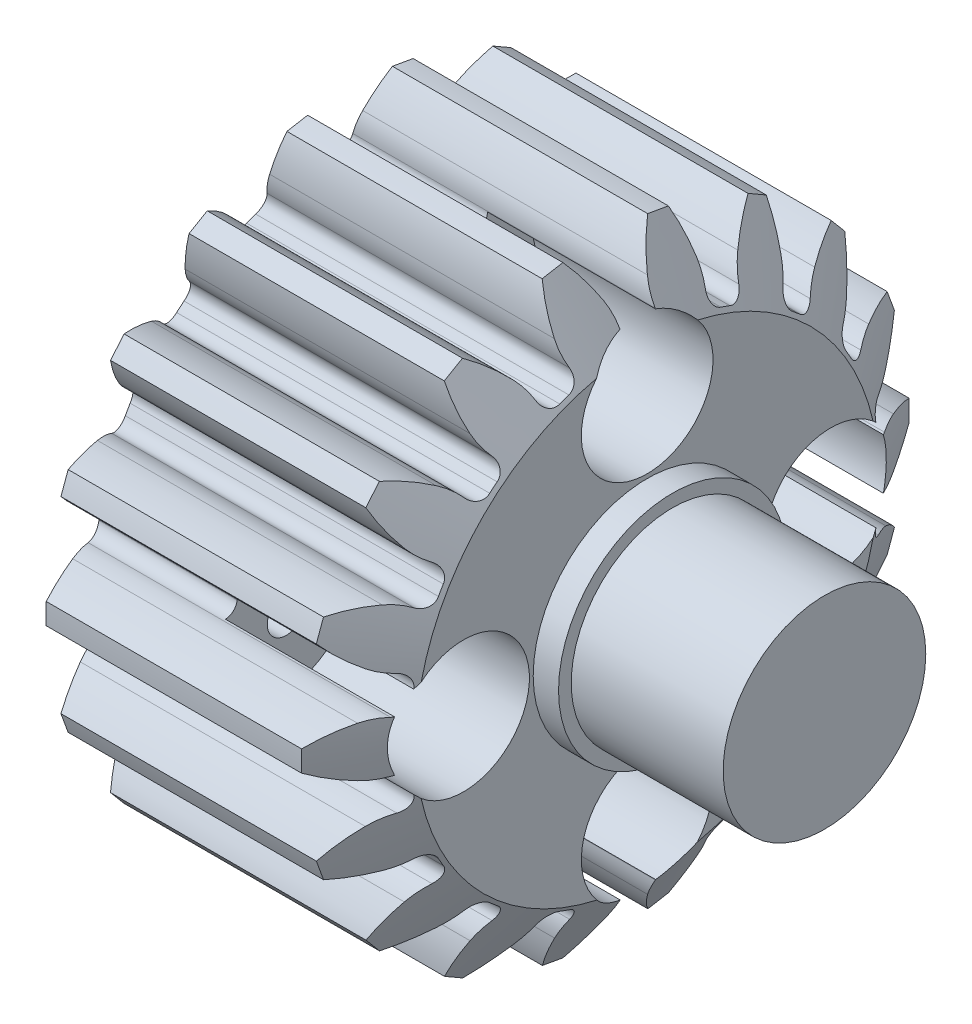
SolidWorks part; units mm, degrees
ref_plane "Front Plane" through (0, 0, 0) normal (0, 0, 1) x (1, 0, 0)
ref_plane "Top Plane" through (0, 0, 0) normal (0, 1, 0) x (1, 0, 0)
ref_plane "Right Plane" through (0, 0, 0) normal (1, 0, 0) x (0, 0, -1)
sketch "Sketch1" plane through (0, 0, 0) normal (1, 0, 0) x (0, 0, -1)
  line L0 (-201.8276, 36.4588) -> (-169.5724, 36.4588) construction
  line L1 (-185.7, 23.0219) -> (-185.7, 49.8958) construction
  line L2 (-185.7, 36.4588) -> (-183.3021, 50.0583) construction
  circle A0 centre (-185.7, 36.4588) radius 9.3 construction
  circle A1 centre (-185.7, 43.7088) radius 0.75
  circle A2 centre (-178.45, 36.4588) radius 0.75
  circle A3 centre (-185.7, 29.2088) radius 0.75
  circle A4 centre (-192.95, 36.4588) radius 0.75
  circle A5 centre (-185.7, 36.4588) radius 12 construction
  arc A7 (-183.2083, 48.1973) -> (-184.0267, 48.3416) centre (-185.7, 36.4588) ccw
  arc A8 (-185.7, 45.7588) -> (-185.5087, 45.7569) centre (-185.7, 36.4588) cw
  arc A9 (-185.5087, 45.7569) -> (-185.0008, 46.2349) centre (-185.4785, 46.2336) ccw
  arc A10 (-185.0008, 46.2349) -> (-184.832, 47.0472) centre (-182.988, 46.2402) cw
  arc A11 (-184.832, 47.0472) -> (-184.0267, 48.3416) centre (-179.9662, 44.9177) cw
  arc A12 (-182.8942, 46.7056) -> (-183.2083, 48.1973) centre (-188.1949, 46.3686) ccw
  arc A13 (-183.0134, 45.8844) -> (-182.8942, 46.7056) centre (-184.9031, 46.5779) ccw
  arc A14 (-182.6997, 45.2616) -> (-183.0134, 45.8844) centre (-182.565, 45.7199) cw
  arc A15 (-182.5192, 45.198) -> (-182.6997, 45.2616) centre (-185.7, 36.4588) ccw
  arc A16 (-182.5192, 45.198) -> (-182.3401, 45.1307) centre (-185.7, 36.4588) cw
  arc A17 (-182.3401, 45.1307) -> (-181.6994, 45.4062) centre (-182.1487, 45.5684) ccw
  arc A18 (-181.6994, 45.4062) -> (-181.2629, 46.1118) centre (-179.8061, 44.7227) cw
  arc A19 (-181.2629, 46.1118) -> (-180.0635, 47.0527) centre (-177.4189, 42.4465) cw
  arc A20 (-179.3437, 46.6371) -> (-180.0635, 47.0527) centre (-185.7, 36.4588) ccw
  arc A21 (-179.5588, 45.128) -> (-179.3437, 46.6371) centre (-184.6551, 46.6243) ccw
  arc A22 (-179.9517, 44.3971) -> (-179.5588, 45.128) centre (-181.4902, 45.6951) ccw
  arc A23 (-179.8699, 43.7045) -> (-179.9517, 44.3971) centre (-179.5866, 44.0891) cw
  arc A24 (-179.7221, 43.5831) -> (-179.8699, 43.7045) centre (-185.7, 36.4588) ccw
  arc A25 (-179.7221, 43.5831) -> (-179.5768, 43.4586) centre (-185.7, 36.4588) cw
  arc A26 (-179.5768, 43.4586) -> (-178.8805, 43.4983) centre (-179.2472, 43.8044) ccw
  arc A27 (-178.8805, 43.4983) -> (-178.229, 44.0121) centre (-177.3351, 42.2085) cw
  arc A28 (-178.229, 44.0121) -> (-176.7801, 44.486) centre (-175.8704, 39.2531) cw
  arc A29 (-176.2459, 43.8493) -> (-176.7801, 44.486) centre (-185.7, 36.4588) ccw
  arc A30 (-176.9642, 42.5048) -> (-176.2459, 43.8493) centre (-181.2413, 45.6539) ccw
  arc A31 (-177.5833, 41.9523) -> (-176.9642, 42.5048) centre (-178.5851, 43.6982) ccw
  arc A32 (-177.7433, 41.2735) -> (-177.5833, 41.9523) centre (-177.3455, 41.538) cw
  arc A33 (-177.646, 41.1088) -> (-177.7433, 41.2735) centre (-185.7, 36.4588) ccw
  arc A34 (-177.646, 41.1088) -> (-177.552, 40.9422) centre (-185.7, 36.4588) cw
  arc A35 (-177.552, 40.9422) -> (-176.8841, 40.7414) centre (-177.1241, 41.1544) ccw
  arc A36 (-176.8841, 40.7414) -> (-176.0962, 41.0013) centre (-175.8731, 39.0008) cw
  arc A37 (-176.0962, 41.0013) -> (-174.5726, 40.9511) centre (-175.5075, 35.7226) cw
  arc A38 (-174.2883, 40.1701) -> (-174.5726, 40.9511) centre (-185.7, 36.4588) ccw
  arc A39 (-175.4232, 39.1523) -> (-174.2883, 40.1701) centre (-178.3653, 43.5744) ccw
  arc A40 (-176.1939, 38.845) -> (-175.4232, 39.1523) centre (-176.5382, 40.8282) ccw
  arc A41 (-176.5764, 38.2618) -> (-176.1939, 38.845) centre (-176.1122, 38.3743) cw
  arc A42 (-176.5413, 38.0738) -> (-176.5764, 38.2618) centre (-185.7, 36.4588) ccw
  arc A43 (-176.5413, 38.0738) -> (-176.51, 37.885) centre (-185.7, 36.4588) cw
  arc A44 (-176.51, 37.885) -> (-175.9511, 37.4679) centre (-176.0353, 37.9381) ccw
  arc A45 (-175.9511, 37.4679) -> (-175.1217, 37.4427) centre (-175.5963, 35.4865) cw
  arc A46 (-175.1217, 37.4427) -> (-173.7072, 36.8744) centre (-176.374, 32.281) cw
  arc A47 (-173.7072, 36.0433) -> (-173.7072, 36.8744) centre (-185.7, 36.4588) ccw
  arc A48 (-175.1217, 35.475) -> (-173.7072, 36.0433) centre (-176.374, 40.6367) ccw
  arc A49 (-175.9511, 35.4498) -> (-175.1217, 35.475) centre (-175.5963, 37.4312) ccw
  arc A50 (-176.51, 35.0327) -> (-175.9511, 35.4498) centre (-176.0353, 34.9796) cw
  arc A51 (-176.5413, 34.8439) -> (-176.51, 35.0327) centre (-185.7, 36.4588) ccw
  arc A52 (-176.5413, 34.8439) -> (-176.5764, 34.6559) centre (-185.7, 36.4588) cw
  arc A53 (-176.5764, 34.6559) -> (-176.1939, 34.0727) centre (-176.1122, 34.5434) ccw
  arc A54 (-176.1939, 34.0727) -> (-175.4232, 33.7653) centre (-176.5382, 32.0895) cw
  arc A55 (-175.4232, 33.7653) -> (-174.2883, 32.7475) centre (-178.3653, 29.3433) cw
  arc A56 (-174.5726, 31.9666) -> (-174.2883, 32.7475) centre (-185.7, 36.4588) ccw
  arc A57 (-176.0962, 31.9164) -> (-174.5726, 31.9666) centre (-175.5075, 37.195) ccw
  arc A58 (-176.8841, 32.1763) -> (-176.0962, 31.9164) centre (-175.8731, 33.9169) ccw
  arc A59 (-177.552, 31.9755) -> (-176.8841, 32.1763) centre (-177.1241, 31.7633) cw
  arc A60 (-177.646, 31.8088) -> (-177.552, 31.9755) centre (-185.7, 36.4588) ccw
  arc A61 (-177.646, 31.8088) -> (-177.7433, 31.6441) centre (-185.7, 36.4588) cw
  arc A62 (-177.7433, 31.6441) -> (-177.5833, 30.9653) centre (-177.3455, 31.3797) ccw
  arc A63 (-177.5833, 30.9653) -> (-176.9642, 30.4129) centre (-178.5851, 29.2195) cw
  arc A64 (-176.9642, 30.4129) -> (-176.2459, 29.0683) centre (-181.2413, 27.2638) cw
  arc A65 (-176.7801, 28.4317) -> (-176.2459, 29.0683) centre (-185.7, 36.4588) ccw
  arc A66 (-178.229, 28.9056) -> (-176.7801, 28.4317) centre (-175.8704, 33.6646) ccw
  arc A67 (-178.8805, 29.4194) -> (-178.229, 28.9056) centre (-177.3351, 30.7092) ccw
  arc A68 (-179.5768, 29.4591) -> (-178.8805, 29.4194) centre (-179.2472, 29.1133) cw
  arc A69 (-179.7221, 29.3346) -> (-179.5768, 29.4591) centre (-185.7, 36.4588) ccw
  arc A70 (-179.7221, 29.3346) -> (-179.8699, 29.2132) centre (-185.7, 36.4588) cw
  arc A71 (-179.8699, 29.2132) -> (-179.9517, 28.5206) centre (-179.5866, 28.8286) ccw
  arc A72 (-179.9517, 28.5206) -> (-179.5588, 27.7897) centre (-181.4902, 27.2226) cw
  arc A73 (-179.5588, 27.7897) -> (-179.3437, 26.2805) centre (-184.6551, 26.2934) cw
  arc A74 (-180.0635, 25.865) -> (-179.3437, 26.2805) centre (-185.7, 36.4588) ccw
  arc A75 (-181.2629, 26.8059) -> (-180.0635, 25.865) centre (-177.4189, 30.4712) ccw
  arc A76 (-181.6994, 27.5115) -> (-181.2629, 26.8059) centre (-179.8061, 28.195) ccw
  arc A77 (-182.3401, 27.787) -> (-181.6994, 27.5115) centre (-182.1487, 27.3493) cw
  arc A78 (-182.5192, 27.7197) -> (-182.3401, 27.787) centre (-185.7, 36.4588) ccw
  arc A79 (-182.5192, 27.7197) -> (-182.6997, 27.6561) centre (-185.7, 36.4588) cw
  arc A80 (-182.6997, 27.6561) -> (-183.0134, 27.0333) centre (-182.565, 27.1978) ccw
  arc A81 (-183.0134, 27.0333) -> (-182.8942, 26.2121) centre (-184.9031, 26.3398) cw
  arc A82 (-182.8942, 26.2121) -> (-183.2083, 24.7204) centre (-188.1949, 26.5491) cw
  arc A83 (-184.0267, 24.5761) -> (-183.2083, 24.7204) centre (-185.7, 36.4588) ccw
  arc A84 (-184.832, 25.8704) -> (-184.0267, 24.5761) centre (-179.9662, 28) ccw
  arc A85 (-185.0008, 26.6828) -> (-184.832, 25.8704) centre (-182.988, 26.6775) ccw
  arc A86 (-185.5087, 27.1608) -> (-185.0008, 26.6828) centre (-185.4785, 26.6841) cw
  arc A87 (-185.7, 27.1588) -> (-185.5087, 27.1608) centre (-185.7, 36.4588) ccw
  arc A88 (-185.7, 27.1588) -> (-185.8913, 27.1608) centre (-185.7, 36.4588) cw
  arc A89 (-185.8913, 27.1608) -> (-186.3992, 26.6828) centre (-185.9215, 26.6841) ccw
  arc A90 (-186.3992, 26.6828) -> (-186.568, 25.8704) centre (-188.412, 26.6775) cw
  arc A91 (-186.568, 25.8704) -> (-187.3733, 24.5761) centre (-191.4338, 28) cw
  arc A92 (-188.1917, 24.7204) -> (-187.3733, 24.5761) centre (-185.7, 36.4588) ccw
  arc A93 (-188.5058, 26.2121) -> (-188.1917, 24.7204) centre (-183.2051, 26.5491) ccw
  arc A94 (-188.3866, 27.0333) -> (-188.5058, 26.2121) centre (-186.4969, 26.3398) ccw
  arc A95 (-188.7003, 27.6561) -> (-188.3866, 27.0333) centre (-188.835, 27.1978) cw
  arc A96 (-188.8808, 27.7197) -> (-188.7003, 27.6561) centre (-185.7, 36.4588) ccw
  arc A97 (-188.8808, 27.7197) -> (-189.0599, 27.787) centre (-185.7, 36.4588) cw
  arc A98 (-189.0599, 27.787) -> (-189.7006, 27.5115) centre (-189.2513, 27.3493) ccw
  arc A99 (-189.7006, 27.5115) -> (-190.1371, 26.8059) centre (-191.5939, 28.195) cw
  arc A100 (-190.1371, 26.8059) -> (-191.3365, 25.865) centre (-193.9811, 30.4712) cw
  arc A101 (-192.0563, 26.2805) -> (-191.3365, 25.865) centre (-185.7, 36.4588) ccw
  arc A102 (-191.8412, 27.7897) -> (-192.0563, 26.2805) centre (-186.7449, 26.2934) ccw
  arc A103 (-191.4483, 28.5206) -> (-191.8412, 27.7897) centre (-189.9098, 27.2226) ccw
  arc A104 (-191.5301, 29.2132) -> (-191.4483, 28.5206) centre (-191.8134, 28.8286) cw
  arc A105 (-191.6779, 29.3346) -> (-191.5301, 29.2132) centre (-185.7, 36.4588) ccw
  arc A106 (-191.6779, 29.3346) -> (-191.8232, 29.4591) centre (-185.7, 36.4588) cw
  arc A107 (-191.8232, 29.4591) -> (-192.5195, 29.4194) centre (-192.1528, 29.1133) ccw
  arc A108 (-192.5195, 29.4194) -> (-193.171, 28.9056) centre (-194.0649, 30.7092) cw
  arc A109 (-193.171, 28.9056) -> (-194.6199, 28.4317) centre (-195.5296, 33.6646) cw
  arc A110 (-195.1541, 29.0683) -> (-194.6199, 28.4317) centre (-185.7, 36.4588) ccw
  arc A111 (-194.4358, 30.4129) -> (-195.1541, 29.0683) centre (-190.1587, 27.2638) ccw
  arc A112 (-193.8167, 30.9653) -> (-194.4358, 30.4129) centre (-192.8149, 29.2195) ccw
  arc A113 (-193.6567, 31.6441) -> (-193.8167, 30.9653) centre (-194.0544, 31.3797) cw
  arc A114 (-193.754, 31.8088) -> (-193.6567, 31.6441) centre (-185.7, 36.4588) ccw
  arc A115 (-193.754, 31.8088) -> (-193.848, 31.9755) centre (-185.7, 36.4588) cw
  arc A116 (-193.848, 31.9755) -> (-194.5159, 32.1763) centre (-194.2759, 31.7633) ccw
  arc A117 (-194.5159, 32.1763) -> (-195.3038, 31.9164) centre (-195.5269, 33.9169) cw
  arc A118 (-195.3038, 31.9164) -> (-196.8274, 31.9666) centre (-195.8925, 37.195) cw
  arc A119 (-197.1117, 32.7475) -> (-196.8274, 31.9666) centre (-185.7, 36.4588) ccw
  arc A120 (-195.9768, 33.7653) -> (-197.1117, 32.7475) centre (-193.0347, 29.3433) ccw
  arc A121 (-195.2061, 34.0727) -> (-195.9768, 33.7653) centre (-194.8618, 32.0895) ccw
  arc A122 (-194.8236, 34.6559) -> (-195.2061, 34.0727) centre (-195.2878, 34.5434) cw
  arc A123 (-194.8587, 34.8439) -> (-194.8236, 34.6559) centre (-185.7, 36.4588) ccw
  arc A124 (-194.8587, 34.8439) -> (-194.89, 35.0327) centre (-185.7, 36.4588) cw
  arc A125 (-194.89, 35.0327) -> (-195.4489, 35.4498) centre (-195.3647, 34.9796) ccw
  arc A126 (-195.4489, 35.4498) -> (-196.2783, 35.475) centre (-195.8037, 37.4312) cw
  arc A127 (-196.2783, 35.475) -> (-197.6928, 36.0433) centre (-195.026, 40.6367) cw
  arc A128 (-197.6928, 36.8744) -> (-197.6928, 36.0433) centre (-185.7, 36.4588) ccw
  arc A129 (-196.2783, 37.4427) -> (-197.6928, 36.8744) centre (-195.026, 32.281) ccw
  arc A130 (-195.4489, 37.4679) -> (-196.2783, 37.4427) centre (-195.8037, 35.4865) ccw
  arc A131 (-194.89, 37.885) -> (-195.4489, 37.4679) centre (-195.3647, 37.9381) cw
  arc A132 (-194.8587, 38.0738) -> (-194.89, 37.885) centre (-185.7, 36.4588) ccw
  arc A133 (-194.8587, 38.0738) -> (-194.8236, 38.2618) centre (-185.7, 36.4588) cw
  arc A134 (-194.8236, 38.2618) -> (-195.2061, 38.845) centre (-195.2878, 38.3743) ccw
  arc A135 (-195.2061, 38.845) -> (-195.9768, 39.1523) centre (-194.8618, 40.8282) cw
  arc A136 (-195.9768, 39.1523) -> (-197.1117, 40.1701) centre (-193.0347, 43.5744) cw
  arc A137 (-196.8274, 40.9511) -> (-197.1117, 40.1701) centre (-185.7, 36.4588) ccw
  arc A138 (-195.3038, 41.0013) -> (-196.8274, 40.9511) centre (-195.8925, 35.7226) ccw
  arc A139 (-194.5159, 40.7414) -> (-195.3038, 41.0013) centre (-195.5269, 39.0008) ccw
  arc A140 (-193.848, 40.9422) -> (-194.5159, 40.7414) centre (-194.2759, 41.1544) cw
  arc A141 (-193.754, 41.1088) -> (-193.848, 40.9422) centre (-185.7, 36.4588) ccw
  arc A142 (-193.754, 41.1088) -> (-193.6567, 41.2735) centre (-185.7, 36.4588) cw
  arc A143 (-193.6567, 41.2735) -> (-193.8167, 41.9523) centre (-194.0544, 41.538) ccw
  arc A144 (-193.8167, 41.9523) -> (-194.4358, 42.5048) centre (-192.8149, 43.6982) cw
  arc A145 (-194.4358, 42.5048) -> (-195.1541, 43.8493) centre (-190.1587, 45.6539) cw
  arc A146 (-194.6199, 44.486) -> (-195.1541, 43.8493) centre (-185.7, 36.4588) ccw
  arc A147 (-193.171, 44.0121) -> (-194.6199, 44.486) centre (-195.5296, 39.2531) ccw
  arc A148 (-192.5195, 43.4983) -> (-193.171, 44.0121) centre (-194.0649, 42.2085) ccw
  arc A149 (-191.8232, 43.4586) -> (-192.5195, 43.4983) centre (-192.1528, 43.8044) cw
  arc A150 (-191.6779, 43.5831) -> (-191.8232, 43.4586) centre (-185.7, 36.4588) ccw
  arc A151 (-191.6779, 43.5831) -> (-191.5301, 43.7045) centre (-185.7, 36.4588) cw
  arc A152 (-191.5301, 43.7045) -> (-191.4483, 44.3971) centre (-191.8134, 44.0891) ccw
  arc A153 (-191.4483, 44.3971) -> (-191.8412, 45.128) centre (-189.9098, 45.6951) cw
  arc A154 (-191.8412, 45.128) -> (-192.0563, 46.6371) centre (-186.7449, 46.6243) cw
  arc A155 (-191.3365, 47.0527) -> (-192.0563, 46.6371) centre (-185.7, 36.4588) ccw
  arc A156 (-190.1371, 46.1118) -> (-191.3365, 47.0527) centre (-193.9811, 42.4465) ccw
  arc A157 (-189.7006, 45.4062) -> (-190.1371, 46.1118) centre (-191.5939, 44.7227) ccw
  arc A158 (-189.0599, 45.1307) -> (-189.7006, 45.4062) centre (-189.2513, 45.5684) cw
  arc A159 (-188.8808, 45.198) -> (-189.0599, 45.1307) centre (-185.7, 36.4588) ccw
  arc A160 (-188.8808, 45.198) -> (-188.7003, 45.2616) centre (-185.7, 36.4588) cw
  arc A161 (-188.7003, 45.2616) -> (-188.3866, 45.8844) centre (-188.835, 45.7199) ccw
  arc A162 (-188.3866, 45.8844) -> (-188.5058, 46.7056) centre (-186.4969, 46.5779) cw
  arc A163 (-188.5058, 46.7056) -> (-188.1917, 48.1973) centre (-183.2051, 46.3686) cw
  arc A164 (-187.3733, 48.3416) -> (-188.1917, 48.1973) centre (-185.7, 36.4588) ccw
  arc A165 (-186.568, 47.0472) -> (-187.3733, 48.3416) centre (-191.4338, 44.9177) ccw
  arc A166 (-186.3992, 46.2349) -> (-186.568, 47.0472) centre (-188.412, 46.2402) ccw
  arc A167 (-185.8913, 45.7569) -> (-186.3992, 46.2349) centre (-185.9215, 46.2336) cw
  arc A168 (-185.7, 45.7588) -> (-185.8913, 45.7569) centre (-185.7, 36.4588) ccw
  point P8 (-185.7, 36.4588)
  point P10 (-185.7, 36.4588)
  point P22 (-185.7, 36.4588)
  point P311 (-185.7, 36.4588)
  dimension "D1" = 7.25
  dimension "D2" = 1.5
  dimension "D4" = 18.6
  dimension "D5" = 24
  dimension "D8" = 18
  dimension "D7" = 10
  dimension "D3" = 4
extrude "Boss-Extrude2" add sketch "Sketch1" along normal blind 12.5 contours A8 A168 A167 A166 A165 A164 A163 A162 A161 A160 A159 A158 A157 A156 A155 A154 A153 A152 A151 A150 A149 A148 A147 A146 A145 A144 A143 A142 A141 A140 A139 A138 A137 A136 A135 A134 A133 A132 A131 A130 A129 A128 A127 A126 A125 A124 A123 A122 A121 A120 A119 region at (0, 36.4588, 185.7)
ref_plane "Plane1" through (0, 36.45, 0) normal (0, 1, 0) x (1, 0, 0)
sketch "Sketch2" plane through (12.5, 0, 0) normal (1, 0, 0) x (0, 0, -1)
  circle A0 centre (-185.7, 43.7088) radius 2.6
  circle A1 centre (-178.45, 36.4588) radius 2.6
  circle A2 centre (-185.7, 29.2088) radius 2.6
  circle A3 centre (-192.95, 36.4588) radius 2.6
  point P3 (-185.7, 36.4588)
  point P4 (0, 0)
  point P14 (-185.7, 36.4588)
  dimension "D1" = 5.2
  dimension "D2" = 4
extrude "Cut-Extrude1" cut sketch "Sketch2" against normal blind 7
sketch "Sketch3" plane through (0, 36.45, 0) normal (0, 1, 0) x (1, 0, 0)
  line L0 (-4.688, -185.7) -> (16.528, -185.7) construction
  line L1 (5.5, -185.7) -> (0, -185.7) construction
  line L2 (12.5, -173.7072) -> (0, -173.7072) construction
  line L3 (12.5, -176.5586) -> (15.9641, -170.5586)
  line L4 (15.9641, -170.5586) -> (9.0359, -170.5586)
  line L5 (9.0359, -170.5586) -> (12.5, -176.5586)
  line L6 (12.5, -175.1217) -> (12.5, -173.7072) construction
  line L7 (0, -170.5586) -> (0, -176.5586)
  line L9 (0, -176.5586) -> (1.6077, -170.5586)
  line L10 (1.6077, -170.5586) -> (0, -170.5586)
  line L11 (0, -176.7801) -> (0, -178.229) construction
  circle A0 centre (12.5, -172.5586) radius 2 construction
  point P17 (0, 0)
  point P19 (0, 0)
  dimension "D1" = 1.1486
  dimension "D2" = 6
  dimension "D3" = 15
revolve "Cut-Revolve1" cut sketch "Sketch3" angle 360 about L0
sketch "Sketch5" plane through (12.5, 0, 0) normal (1, 0, 0) x (0, 0, -1)
  circle A0 centre (-185.7, 36.45) radius 4
  dimension "D1" = 8
extrude "Boss-Extrude3" add sketch "Sketch5" along normal blind 7
sketch "Sketch6" plane through (12.5, 0, 0) normal (1, 0, 0) x (0, 0, -1)
  circle A0 centre (-185.7, 36.45) radius 4.5
  dimension "D1" = 9
extrude "Boss-Extrude4" add sketch "Sketch6" along normal blind 1
